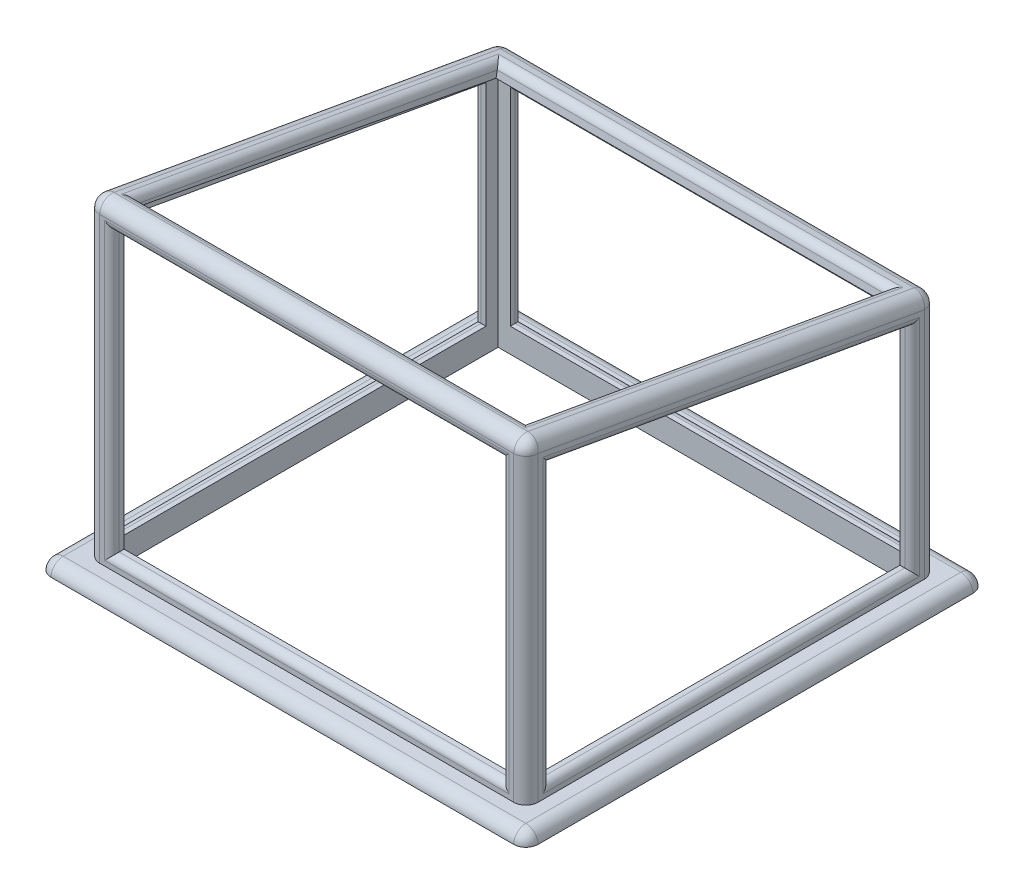
SolidWorks part; units mm, degrees
ref_plane "Front Plane" through (0, 0, 0) normal (0, 0, 1) x (1, 0, 0)
ref_plane "Top Plane" through (0, 0, 0) normal (0, 1, 0) x (1, 0, 0)
ref_plane "Right Plane" through (0, 0, 0) normal (1, 0, 0) x (0, 0, -1)
sketch "Sketch1" plane through (0, 0, 0) normal (0, 1, 0) x (1, 0, 0)
  line L0 (-5, 163.6) -> (175, 163.6)
  line L1 (0, 0) -> (170, 0)
  line L2 (0, 0) -> (0, 158.6)
  line L3 (0, 158.6) -> (170, 158.6)
  line L4 (170, 0) -> (170, 158.6)
  line L5 (175, -5) -> (175, 163.6)
  line L6 (-5, -5) -> (175, -5)
  line L7 (-5, -5) -> (-5, 163.6)
  line L8 (5, 153.6) -> (165, 153.6)
  line L9 (165, 5) -> (165, 153.6)
  line L10 (5, 5) -> (165, 5)
  line L11 (5, 5) -> (5, 153.6)
  dimension "D1" = 158.6
  dimension "D2" = 170
  dimension "D3" = 5
  dimension "D4" = 5
extrude "Boss-Extrude1" add sketch "Sketch1" along normal blind 135 contours L7 L6 L5 L0 L4 L1 L2 L3 region at (85, 0, -161.1337)
extrude "Boss-Extrude2" add sketch "Sketch1<3>" along normal blind 135 contours L1 L4 L3 L2 L10 L11 L8 L9 | L11 L10 L9 L8 region at (2.325, 0, -79.3) region at (85, 0, -79.3)
sketch "Sketch1<3>" plane through (0, 0, 0) normal (0, 1, 0) x (1, 0, 0) same geometry as "Sketch1"
sketch "Sketch2" plane through (175, 0, 0) normal (1, 0, 0) x (0, 0, -1)
  line L0 (-5, 135) -> (163.6, 135)
  line L1 (163.6, 135) -> (163.6, 105)
  line L2 (163.6, 135) -> (163.6, 0) construction
  line L3 (163.6, 105) -> (-5, 135)
  dimension "D1" = 30
extrude "Cut-Extrude1" cut sketch "Sketch2" against normal blind 180
sketch "Sketch3" plane through (0, 129.9945, -23.1307) normal (0, 0.9845, -0.1752) x (1, 0, 0)
  line L20 (-15, 152.6757) -> (-15, -38.5726)
  line L21 (-5, 142.6757) -> (175, 142.6757)
  line L22 (-5, 142.6757) -> (-5, -28.5726)
  line L23 (-5, -28.5726) -> (175, -28.5726)
  line L24 (175, 142.6757) -> (175, -28.5726)
  line L25 (-15, -38.5726) -> (185, -38.5726)
  line L26 (185, 152.6757) -> (185, -38.5726)
  line L27 (-15, 152.6757) -> (185, 152.6757)
  line L28 (5, 132.6757) -> (5, -18.5726)
  line L29 (5, -18.5726) -> (165, -18.5726)
  line L30 (165, 132.6757) -> (165, -18.5726)
  line L31 (5, 132.6757) -> (165, 132.6757)
  dimension "D1" = 10
  dimension "D2" = 10
extrude "Cut-Extrude2" cut sketch "Sketch3" against normal blind 10 contours L31 L28 L29 L30 region at (85, 120, -79.3)
sketch "Sketch4" plane through (0, 0, 0) normal (0, -1, 0) x (1, 0, 0)
  line L0 (180, 10) -> (180, -168.6)
  line L1 (175, 5) -> (-5, 5)
  line L2 (175, 5) -> (175, -163.6)
  line L3 (175, -163.6) -> (-5, -163.6)
  line L4 (-5, 5) -> (-5, -163.6)
  line L5 (180, -168.6) -> (-10, -168.6)
  line L6 (-10, 10) -> (-10, -168.6)
  line L7 (180, 10) -> (-10, 10)
  line L8 (170, 0) -> (170, -158.6)
  line L9 (170, -158.6) -> (0, -158.6)
  line L10 (0, 0) -> (0, -158.6)
  line L11 (170, 0) -> (0, 0)
  dimension "D1" = 5
  dimension "D2" = 5
extrude "Cut-Extrude3" cut sketch "Sketch4" against normal blind 100 contours L8 L11 L10 L9 region at (85, 0, -79.3)
sketch "Sketch5" plane through (0, 0, 0) normal (1, 0, 0) x (0, 0, -1)
  line L0 (163.6, 0) -> (158.6, 0)
  line L1 (-5, 0) -> (163.6, 0) construction
  line L2 (158.6, 0) -> (158.6, 100)
  line L3 (158.6, 100) -> (0, 100)
  line L4 (0, 100) -> (0, 0)
  line L5 (0, 0) -> (-5, 0)
  line L6 (0, 100) -> (0, 130)
  line L7 (0, 130) -> (158.6, 100)
  dimension "D1" = 5
  dimension "D2" = 5
  dimension "D3" = 100
  dimension "D4" = 30
  dimension "D5" = 130
extrude "Cut-Extrude5" cut sketch "Sketch5" along normal blind 170 contours L7 L6 L3 region at (0, 110, -52.8667)
sketch "Sketch6" plane through (175, 0, 0) normal (1, 0, 0) x (0, 0, -1)
  line L0 (-5, 135) -> (-5, 0)
  line L1 (-5, 0) -> (163.6, 0)
  line L2 (163.6, 0) -> (163.6, 105)
  line L3 (163.6, 105) -> (-5, 135)
  line L4 (168.6, 109.1889) -> (-10, 140.9682)
  line L5 (-10, 140.9682) -> (-10, -5)
  line L6 (-10, -5) -> (168.6, -5)
  line L7 (168.6, -5) -> (168.6, 109.1889)
  line L8 (153.6, 96.6223) -> (5, 123.0636)
  line L9 (5, 123.0636) -> (5, 10)
  line L10 (5, 10) -> (153.6, 10)
  line L11 (153.6, 10) -> (153.6, 96.6223)
  dimension "D1" = 5
  dimension "D2" = 10
extrude "Cut-Extrude6" cut sketch "Sketch6" against normal blind 180 contours L10 L11 L8 L9 region at (175, 60.2132, -76.0205)
sketch "Sketch7" plane through (0, 0, 5) normal (0, 0, 1) x (1, 0, 0)
  line L0 (185, 145) -> (185, -10)
  line L1 (175, 135) -> (-5, 135)
  line L2 (175, 135) -> (175, 0)
  line L3 (175, 0) -> (-5, 0)
  line L4 (-5, 135) -> (-5, 0)
  line L5 (185, -10) -> (-15, -10)
  line L6 (-15, 145) -> (-15, -10)
  line L7 (185, 145) -> (-15, 145)
  line L8 (165, 125) -> (165, 10)
  line L9 (165, 10) -> (5, 10)
  line L10 (5, 125) -> (5, 10)
  line L11 (165, 125) -> (5, 125)
  dimension "D1" = 10
  dimension "D2" = 10
extrude "Cut-Extrude7" cut sketch "Sketch7" against normal blind 10 contours L8 L11 L10 L9 region at (85, 67.5, 5)
sketch "Sketch8" plane through (0, 0, -163.6) normal (0, 0, -1) x (-1, 0, 0)
  line L0 (5, 105) -> (5, 0) construction
  line L1 (-175, 105) -> (5, 105)
  line L2 (-175, 105) -> (-175, 0)
  line L3 (-175, 0) -> (5, 0)
  line L4 (5, 105) -> (5, 0)
  line L5 (-185, 115) -> (-185, -10)
  line L6 (-185, -10) -> (15, -10)
  line L7 (15, 115) -> (15, -10)
  line L8 (-185, 115) -> (15, 115)
  line L9 (-165, 95) -> (-165, 10)
  line L10 (-165, 10) -> (-5, 10)
  line L11 (-5, 95) -> (-5, 10)
  line L12 (-165, 95) -> (-5, 95)
  dimension "D1" = 10
  dimension "D2" = 10
extrude "Cut-Extrude8" cut sketch "Sketch8" against normal blind 10 contours L12 L9 L10 L11 region at (85, 52.5, -163.6)
fillet "Fillet2" radius 3 4 edges at (5, 120, -79.3) (85, 133.2482, -4.8454) (85, 106.7518, -153.7546) (165, 120, -79.3)
fillet "Fillet3" radius 3 16 edges at (5, 52.5, -163.6) (165, 52.5, -163.6) (85, 10, -163.6) (85, 95, -163.6) (-5, 66.5318, -5) (-5, 10, -79.3) (-5, 53.3111, -153.6) (-5, 109.8429, -79.3) (175, 10, -79.3) (175, 53.3111, -153.6) (175, 109.8429, -79.3) (175, 66.5318, -5) (85, 10, 5) (165, 67.5, 5) (85, 125, 5) (5, 67.5, 5)
sketch "Sketch9" plane through (0, 0, -163.6) normal (0, 0, -1) x (-1, 0, 0)
  line L0 (5, 105) -> (5, 0) construction
  line L1 (-175, 0) -> (5, 0)
  line L2 (-175, 0) -> (-175, 5)
  line L3 (-175, 5) -> (5, 5)
  line L4 (5, 0) -> (5, 5)
  dimension "D1" = 5
extrude "Boss-Extrude3" add sketch "Sketch9" along normal blind 10
sketch "Sketch10" plane through (0, 0, 5) normal (0, 0, 1) x (1, 0, 0)
  line L1 (-5, 0) -> (175, 0)
  line L2 (-5, 0) -> (-5, 5)
  line L3 (-5, 5) -> (175, 5)
  line L4 (175, 0) -> (175, 5)
extrude "Boss-Extrude4" add sketch "Sketch10" along normal blind 10
sketch "Sketch11" plane through (-5, 0, 0) normal (-1, 0, 0) x (0, 0, 1)
  line L1 (-173.6, 5) -> (15, 5)
  line L2 (-173.6, 5) -> (-173.6, 0)
  line L3 (-173.6, 0) -> (15, 0)
  line L4 (15, 5) -> (15, 0)
extrude "Boss-Extrude5" add sketch "Sketch11" along normal blind 10
sketch "Sketch12" plane through (175, 0, 0) normal (1, 0, 0) x (0, 0, -1)
  line L1 (-15, 5) -> (173.6, 5)
  line L2 (-15, 5) -> (-15, 0)
  line L3 (-15, 0) -> (173.6, 0)
  line L4 (173.6, 5) -> (173.6, 0)
extrude "Boss-Extrude6" add sketch "Sketch12" along normal blind 10
fillet "Fillet4" radius 5 8 edges at (-5, 70, 5) (-5, 120, -79.3) (-5, 55, -163.6) (175, 55, -163.6) (85, 105, -163.6) (85, 135, 5) (175, 120, -79.3) (175, 70, 5)
fillet "Fillet5" radius 5 4 edges at (185, 5, -79.3) (85, 5, -173.6) (-15, 5, -79.3) (85, 5, 15)
